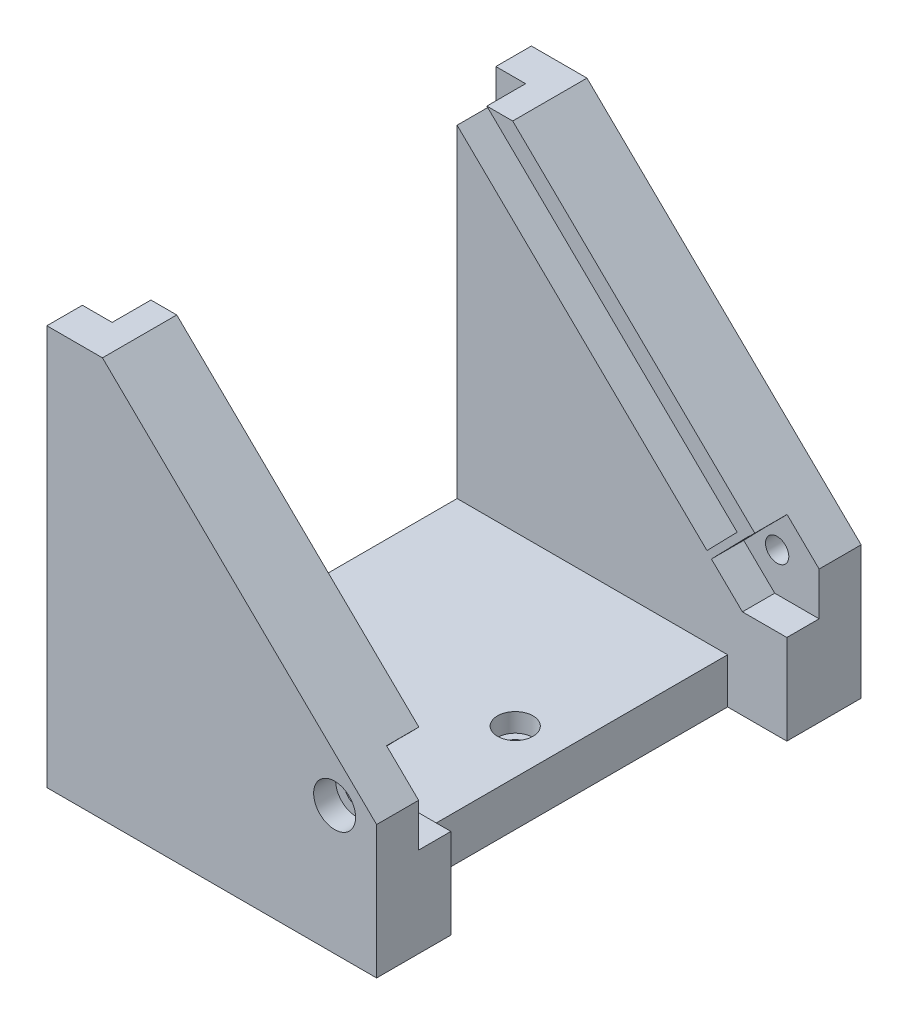
SolidWorks part; units mm, degrees
ref_plane "Plan de face" through (0, 0, 0) normal (0, 0, 1) x (1, 0, 0)
ref_plane "Plan de dessus" through (0, 0, 0) normal (0, 1, 0) x (1, 0, 0)
ref_plane "Plan de droite" through (0, 0, 0) normal (1, 0, 0) x (0, 0, -1)
sketch "Esquisse1" plane through (0, 0, 0) normal (0, 0, 1) x (1, 0, 0)
  line L0 (0, 0) -> (-51.0417, 0)
  line L1 (-51.0417, 0) -> (-51.0417, 61.9186)
  line L2 (-51.0417, 61.9186) -> (-42.4369, 61.9186)
  line L3 (-42.4369, 61.9186) -> (0, 20.5732)
  line L4 (0, 20.5732) -> (0, 0)
  line L5 (-46.4369, 61.9186) -> (-51.0417, 61.9186)
  line L6 (-51.0417, 61.9186) -> (-51.0417, 57.0518)
  line L7 (-51.0417, 57.0518) -> (-12.3642, 19.3692)
  line L8 (-12.3642, 19.3692) -> (-7.6893, 24.1676)
  line L9 (-7.6893, 24.1676) -> (-46.4369, 61.9186)
  line L10 (-4.9631, 25.4087) -> (-5.8001, 24.5496)
  line L11 (-5.8001, 24.5496) -> (-5.8321, 24.5807)
  line L12 (-5.8321, 24.5807) -> (-11.6769, 18.5816)
  line L13 (-11.6769, 18.5816) -> (-6.871, 13.8992)
  line L14 (-6.871, 13.8992) -> (0, 13.8992)
  line L15 (0, 13.8992) -> (0, 20.5732)
  line L16 (0, 20.5732) -> (-4.9631, 25.4087)
  line L17 (-51.0417, 57.0518) -> (-51.0417, 7.0031)
  line L18 (-51.0417, 7.0031) -> (-9.1633, 7.0031)
  line L19 (-9.1633, 7.0031) -> (-9.1633, 0)
  line L20 (-9.1633, 0) -> (0, 0)
  line L21 (0, 0) -> (0, 13.8992)
  line L22 (0, 13.8992) -> (-6.871, 13.8992)
  line L23 (-6.871, 13.8992) -> (-11.6769, 18.5816)
  line L24 (-11.6769, 18.5816) -> (-5.8321, 24.5807)
  line L25 (-5.8321, 24.5807) -> (-5.8001, 24.5496)
  line L26 (-5.8001, 24.5496) -> (-4.9631, 25.4087)
  line L27 (-4.9631, 25.4087) -> (-42.4369, 61.9186)
  line L28 (-42.4369, 61.9186) -> (-46.4369, 61.9186)
  line L29 (-46.4369, 61.9186) -> (-7.6893, 24.1676)
  line L30 (-7.6893, 24.1676) -> (-12.3642, 19.3692)
  line L31 (-12.3642, 19.3692) -> (-51.0417, 57.0518)
  circle A1 centre (-6.5, 19.8992) radius 1.8
  dimension "D1" = 3.6
  dimension "D2" = 4.9631
  dimension "D3" = 5.8001
  dimension "D4" = 5.8321
  dimension "D5" = 6.5
  dimension "D6" = 6.871
  dimension "D7" = 7.6893
  dimension "D8" = 9.1633
  dimension "D9" = 11.6769
  dimension "D10" = 12.3642
  dimension "D11" = 42.4369
  dimension "D12" = 46.4369
  dimension "D13" = 51.0417
  dimension "D14" = 7.0031
  dimension "D15" = 13.8992
  dimension "D16" = 18.5816
  dimension "D18" = 19.8992
extrude "Boss.-Extru.1" add sketch "Esquisse1" along normal blind 5.5 contours L8 L9 L2 L1 L7 region at (-29.9864, 41.2179, 0)
extrude "Boss.-Extru.2" add sketch "Esquisse1<3>" along normal blind 6.5 separate body contours L13 L14 L4 L3 L10 L11 L12 A1 region at (-4.7338, 18.5761, 0)
sketch "Esquisse1<3>" plane through (0, 0, 0) normal (0, 0, 1) x (1, 0, 0) same geometry as "Esquisse1"
extrude "Boss.-Extru.3" add sketch "Esquisse1<5>" along normal blind 11.5 contours L18 L19 L0 L4 L14 L13 L12 L11 L10 L3 L2 L9 L8 L7 L1 region at (-31.2714, 24.5693, 0)
sketch "Esquisse1<5>" plane through (0, 0, 0) normal (0, 0, 1) x (1, 0, 0) same geometry as "Esquisse1"
extrude "Boss.-Extru.4" add sketch "Esquisse1<6>" along normal blind 63.5 contours L19 L18 L1 L0 region at (-30.1025, 3.5016, 0)
sketch "Esquisse1<6>" plane through (0, 0, 0) normal (0, 0, 1) x (1, 0, 0) same geometry as "Esquisse1"
ref_plane "Plan1" through (0, 0, 37.5) normal (0, 0, 1) x (1, 0, 0)
mirror "Symétrie2" about plane through (0, 0, 37.5) normal (0, 0, 1) of bodies 104
sketch "Esquisse4" plane through (0, 7.0031, 0) normal (0, 1, 0) x (1, 0, 0)
  line L0 (-28.0729, -37.5) -> (28.0729, -37.5) construction
  line L1 (-51.0417, -63.5) -> (-51.0417, -11.5) construction
  point P0 (-45.0417, -37.5)
  point P4 (-16.0417, -37.5)
  dimension "D1" = 6
  dimension "D2" = 29
hole_wizard "Chambrage pour vis à six pans creux M2.51" positions "Esquisse4" profile "Esquisse3" counterbore size "M2.5" standard "ISO" end condition through all
sketch "Esquisse3" plane through (-45.0417, 7.0031, 37.5) normal (1, 0, 0) x (0, 0, 1)
  line L0 (0, 0) -> (0, 7.0031)
  line L1 (0, 7.0031) -> (1.55, 7.0031)
  line L3 (1.55, 7.0031) -> (1.55, 2.9)
  line L4 (1.55, 2.9) -> (2.75, 2.9)
  line L5 (2.75, 2.9) -> (2.75, 0)
  line L7 (2.75, 0) -> (0, 0)
  line L11 (0, -6.35) -> (0, 107.95) construction
  dimension "Diamètre du perçage jusqu'au prochain" = 3.1
  dimension "Profondeur du perçage jusqu'au prochain" = 7.0031
  dimension "Diamètre du chambrage" = 5.5
  dimension "Profondeur du chambrage" = 2.9
sketch "Esquisse7" plane through (0, 0, 0) normal (0, 0, -1) x (-1, 0, 0)
  point P0 (6.5, 19.8992)
hole_wizard "Chambrage pour vis à six pans creux M31" positions "Esquisse7" profile "Esquisse6" counterbore size "M3" standard "ISO" end condition through all
sketch "Esquisse6" plane through (-6.5, 19.8992, 0) normal (1, 0, 0) x (0, 1, 0)
  line L0 (0, 0) -> (0, 75)
  line L1 (0, 75) -> (1.8, 75)
  line L3 (1.8, 75) -> (1.8, 3.4)
  line L4 (1.8, 3.4) -> (3.25, 3.4)
  line L5 (3.25, 3.4) -> (3.25, 0)
  line L7 (3.25, 0) -> (0, 0)
  line L11 (0, -6.35) -> (0, 107.95) construction
  dimension "Diamètre du perçage jusqu'au prochain" = 3.6
  dimension "Profondeur du perçage jusqu'au prochain" = 75
  dimension "Diamètre du chambrage" = 6.5
  dimension "Profondeur du chambrage" = 3.4
mirror "Symétrie3" about plane through (0, 0, 37.5) normal (0, 0, 1) of "Chambrage pour vis à six pans creux M31"
